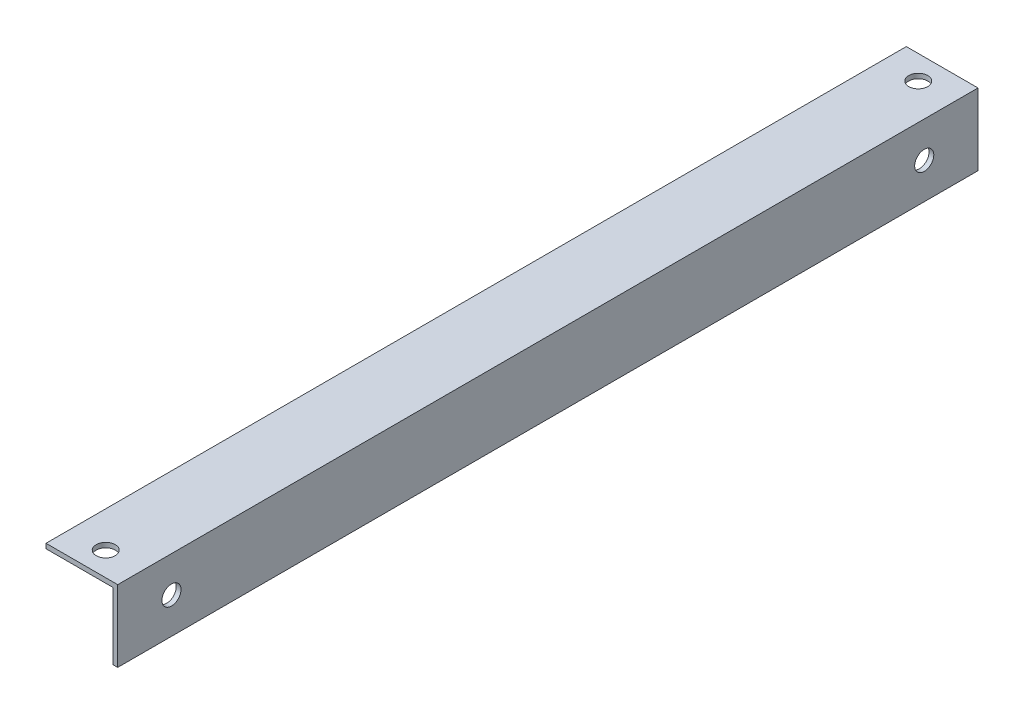
SolidWorks part; units mm, degrees
ref_plane "Ön Düzlem" through (0, 0, 0) normal (0, 0, 1) x (1, 0, 0)
ref_plane "Üst Düzlem" through (0, 0, 0) normal (0, 1, 0) x (1, 0, 0)
ref_plane "Sağ Düzlem" through (0, 0, 0) normal (1, 0, 0) x (0, 0, -1)
sketch "Sketch1" plane through (0, 0, 0) normal (0, 0, 1) x (1, 0, 0)
  line L0 (0, 0) -> (-30, 0)
  line L1 (0, 0) -> (0, -30)
  line L2 (-2, -2) -> (-2, -30)
  line L3 (-2, -2) -> (-30, -2)
  line L4 (-30, 0) -> (-30, -2)
  line L5 (-2, -30) -> (0, -30)
  dimension "D1" = 30
  dimension "D2" = 2
extrude "Boss-Extrude1" add sketch "Sketch1" along normal mid plane 360
sketch "Sketch2" plane through (0, 0, 0) normal (0, 1, 0) x (1, 0, 0)
  line L0 (-15, 180) -> (-15, 170) construction
  line L1 (0, 180) -> (-30, 180) construction
  circle A0 centre (-15, 170) radius 4
  dimension "D1" = 8
  dimension "D2" = 10
extrude "Cut-Extrude1" cut sketch "Sketch2" against normal up to next
sketch "Sketch3" plane through (0, 0, 0) normal (1, 0, 0) x (0, 0, -1)
  line L0 (180, -15) -> (157.5, -15) construction
  line L2 (180, -30) -> (180, 0) construction
  circle A0 centre (157.5, -15) radius 4
  dimension "D1" = 8
  dimension "D2" = 22.5
extrude "Cut-Extrude2" cut sketch "Sketch3" against normal up to next
mirror "Mirror1" about plane through (0, 0, 0) normal (0, 0, 1) of "Cut-Extrude2", "Cut-Extrude1"
ref_axis "Axis1" through (-15, -2, 170) along (0, 1, 0)
ref_axis "Axis2" through (-2, -15, 157.5) along (1, 0, 0)
ref_axis "Axis3" through (-15, -2, -170) along (0, 1, 0)
ref_axis "Axis4" through (-2, -15, -157.5) along (1, 0, 0)
